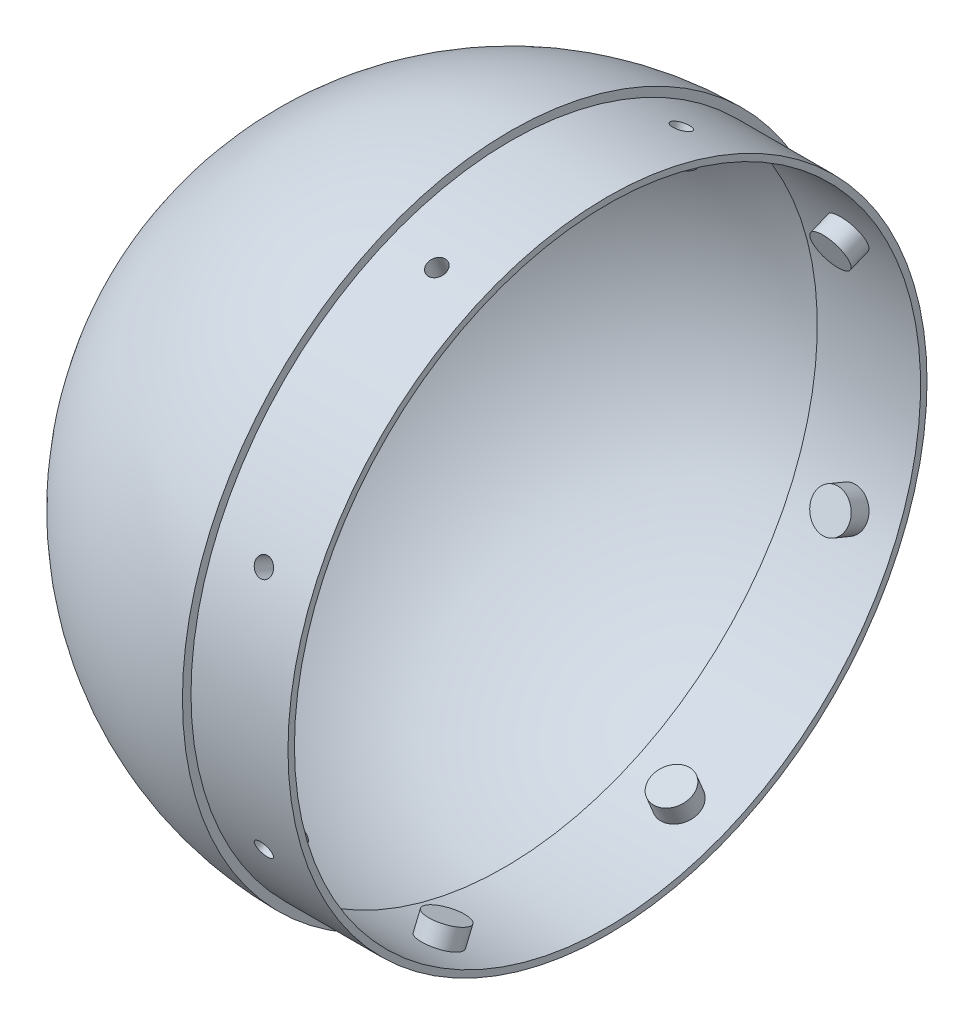
SolidWorks part; units mm, degrees
ref_plane "Front Plane" through (0, 0, 0) normal (0, 0, 1) x (1, 0, 0)
ref_plane "Top Plane" through (0, 0, 0) normal (0, 1, 0) x (1, 0, 0)
ref_plane "Right Plane" through (0, 0, 0) normal (1, 0, 0) x (0, 0, -1)
sketch "Dome Sketch" plane through (0, 0, 0) normal (0, 0, 1) x (1, 0, 0)
  line L0 (-200, 0) -> (100, 0) construction
  line L1 (30, 97) -> (30, 99)
  line L2 (30, 99) -> (-0.05, 99)
  line L3 (-0.05, 99) -> (-0.05, 101.65)
  line L4 (-101.65, 0) -> (-99.65, 0)
  line L5 (-2, 99.6299) -> (-2, 97)
  line L6 (-2, 97) -> (30, 97)
  arc A0 (-0.05, 101.65) -> (-101.65, 0) centre (0, 0) ccw
  arc A1 (-99.65, 0) -> (-2, 99.6299) centre (0, 0) cw
revolve "Dome" add sketch "Dome Sketch" angle 360 about L0
ref_axis "Engine Axis" through (36.5825, 0, 0) along (-1, 0, 0)
ref_plane "Clock Plane 22.5" through (0, 0, 0) normal (0, -0.9239, -0.3827) x (-1, 0, 0)
sketch "Boss Sketch" plane through (0, 0, 0) normal (0, -0.9239, -0.3827) x (-1, 0, 0)
  circle A0 centre (-15, 0) radius 6
extrude "Boss" add sketch "Boss Sketch" against normal blind 6.5 from offset 91 offset against normal yes
sketch "Insert Hole Sketch" plane through (0, 0, 0) normal (0, -0.9239, -0.3827) x (-1, 0, 0)
  circle A0 centre (-15, 0) radius 2.8
extrude "Insert Hole" cut sketch "Insert Hole Sketch" against normal blind 8 from offset 92 offset against normal yes
pattern_circular "Bosses and Holes x8" count 8 over 360 about axis through (36.5825, 0, 0) along (-1, 0, 0) of "Boss", "Insert Hole"
